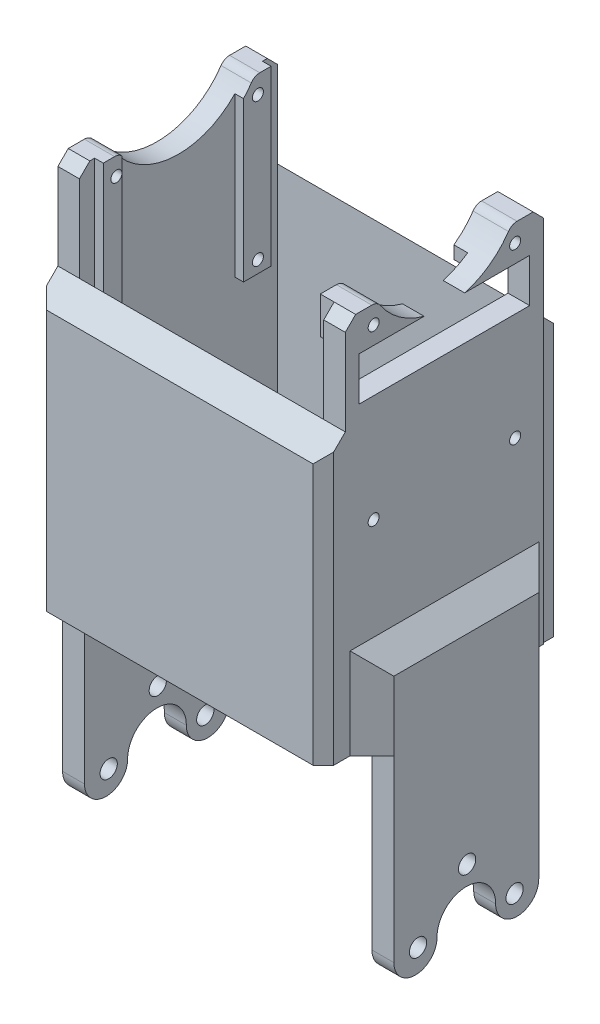
SolidWorks part; units mm, degrees
material "PLA"
ref_plane "Front Plane" through (0, 0, 0) normal (0, 0, 1) x (1, 0, 0)
ref_plane "Top Plane" through (0, 0, 0) normal (0, 1, 0) x (1, 0, 0)
ref_plane "Right Plane" through (0, 0, 0) normal (1, 0, 0) x (0, 0, -1)
sketch "Sketch1" plane through (0, 0, 0) normal (0, 0, 1) x (1, 0, 0)
  line L0 (0, 0) -> (35.4, 0)
  line L1 (35.4, 0) -> (35.4, 51.875)
  line L2 (0, 0) -> (-3.125, 0) construction
  line L3 (35.4, 0) -> (38.525, 0) construction
  line L4 (-3.125, -3.125) -> (38.525, -3.125)
  line L5 (38.525, -3.125) -> (38.525, 51.875)
  line L6 (-3.125, -3.125) -> (-3.125, 51.875)
  line L7 (0, 0) -> (0, 51.875)
  line L8 (0, 51.875) -> (-3.125, 51.875)
  line L9 (35.4, 51.875) -> (38.525, 51.875)
  dimension "D1" = 35.4
  dimension "D2" = 3.125
  dimension "D3" = 3.125
  dimension "D4" = 3.125
  dimension "D5" = 55
  dimension "D6" = 55
extrude "Boss-Extrude1" add sketch "Sketch1" along normal blind 28.72
sketch "Sketch2" plane through (38.525, 0, 0) normal (1, 0, 0) x (0, 0, -1)
  line L0 (-28.72, 46.285) -> (0, 46.285) construction
  line L1 (-28.72, -3.125) -> (-28.72, 51.875) construction
  line L2 (0, -3.125) -> (0, 51.875) construction
  line L3 (-28.72, 51.875) -> (0, 51.875) construction
  line L4 (-14.36, 46.285) -> (-14.36, 57.485) construction
  circle A0 centre (-14.36, 57.485) radius 11.2
  dimension "D1" = 5.59
  dimension "D2" = 11.2
extrude "Cut-Extrude1" cut sketch "Sketch2" against normal through all
fillet "Fillet2" radius 1.5 4 edges at (-1.5625, 51.875, 24.0537) (-1.5625, 51.875, 4.6663) (36.9625, 51.875, 4.6663) (36.9625, 51.875, 24.0537)
sketch "Sketch3" plane through (0, 0, 0) normal (0, 0, -1) x (-1, 0, 0)
  line L1 (-38.325, 37.875) -> (3.125, 37.875)
  line L2 (-38.325, 37.875) -> (-38.325, -3.125)
  line L3 (-38.325, -3.125) -> (3.125, -3.125)
  line L4 (3.125, 37.875) -> (3.125, -3.125)
extrude "Boss-Extrude2" add sketch "Sketch3" along normal blind 3.175
sketch "Sketch4" plane through (0, 0, 28.72) normal (0, 0, 1) x (1, 0, 0)
  line L1 (-3.125, 37.875) -> (38.525, 37.875)
  line L2 (-3.125, 37.875) -> (-3.125, -3.125)
  line L3 (-3.125, -3.125) -> (38.525, -3.125)
  line L4 (38.525, 37.875) -> (38.525, -3.125)
extrude "Boss-Extrude3" add sketch "Sketch4" along normal blind 3.175
chamfer "Chamfer1" distance 3.175 angle 45 2 edges at (17.6, 37.875, -3.175) (17.7, 37.875, 31.895)
chamfer "Chamfer2" distance 1.5 angle 45 4 edges at (-1.5625, 51.875, 0) (36.9625, 51.875, 0) (-1.5625, 51.875, 28.72) (36.9625, 51.875, 28.72)
chamfer "Chamfer3" distance 1.5 angle 45 4 edges at (-3.125, 15.7875, -3.175) (38.325, 15.7875, -3.175) (38.525, 15.7875, 31.895) (-3.125, 15.7875, 31.895)
sketch "Sketch5" plane through (0, 0, 0) normal (1, 0, 0) x (0, 0, -1)
  line L0 (-3.8368, 51.875) -> (-1.5, 51.875) construction
  line L2 (-2.2006, 51.875) -> (-2.2006, 26.7908)
  line L3 (-2.2006, 26.7908) -> (-6.2006, 26.7908)
  line L4 (-6.2006, 49.8127) -> (-6.2006, 26.7908)
  line L6 (-26.5194, 51.875) -> (-26.5194, 26.7908)
  line L7 (-26.5194, 26.7908) -> (-23.7797, 26.7908)
  line L8 (-23.7797, 51.4262) -> (-23.7797, 26.7908)
  line L9 (-27.22, 51.875) -> (-24.8832, 51.875) construction
  line L10 (-3.8368, 51.875) -> (-2.2006, 51.875)
  line L11 (-26.5194, 51.875) -> (-24.8832, 51.875)
  circle A0 centre (-24.61, 49.2608) radius 0.8
  circle A1 centre (-24.61, 28.5608) radius 0.8
  circle A2 centre (-4.11, 28.5608) radius 0.8
  circle A3 centre (-4.11, 49.2608) radius 0.8
  arc A4 (-3.8368, 51.875) -> (-5.0797, 51.2148) centre (-3.8368, 50.375) ccw construction
  arc A5 (-23.6403, 51.2148) -> (-5.0797, 51.2148) centre (-14.36, 57.485) ccw construction
  arc A6 (-23.6403, 51.2148) -> (-24.8832, 51.875) centre (-24.8832, 50.375) ccw construction
  arc A7 (-3.8368, 51.875) -> (-5.0797, 51.2148) centre (-3.8368, 50.375) ccw
  arc A8 (-23.6403, 51.2148) -> (-23.7797, 51.4262) centre (-14.36, 57.485) ccw
  arc A9 (-23.6403, 51.2148) -> (-24.8832, 51.875) centre (-24.8832, 50.375) ccw
  arc A10 (-6.2006, 49.8127) -> (-5.0797, 51.2148) centre (-14.36, 57.485) ccw
  line M8 (-1.5, 51.875) -> (-3.8368, 51.875)
  arc M9 (-3.8368, 51.875) -> (-5.0797, 51.2148) centre (-3.8368, 50.375) ccw
  arc M10 (-5.0797, 51.2148) -> (-23.6403, 51.2148) centre (-14.36, 57.485) cw
  arc M11 (-23.6403, 51.2148) -> (-24.8832, 51.875) centre (-24.8832, 50.375) ccw
  line M12 (-24.8832, 51.875) -> (-27.22, 51.875)
extrude "Boss-Extrude4" add sketch "Sketch5" along normal blind 1.25 contours L4 L3 L2 A3 A2 M10 M8 M9 | L8 L6 L7 A1 A0 M11 M12 region at (0, 39.3275, 25.186) region at (0, 39.1233, 4.1775)
sketch "Sketch6" plane through (0, 0, 0) normal (1, 0, 0) x (0, 0, -1)
  circle A0 centre (-24.61, 49.2608) radius 0.8
  circle A1 centre (-24.61, 28.5608) radius 0.8
  circle A2 centre (-4.11, 28.5608) radius 0.8
  circle A3 centre (-4.11, 49.2608) radius 0.8
extrude "Cut-Extrude2" cut sketch "Sketch6" against normal up to next
sketch "Sketch7" plane through (0, -3.125, 0) normal (0, -1, 0) x (1, 0, 0)
  line L0 (11.7, 22.36) -> (23.7, 22.36) construction
  line L1 (23.7, 22.36) -> (23.7, 6.36) construction
  line L2 (23.7, 6.36) -> (11.7, 6.36) construction
  line L3 (11.7, 6.36) -> (11.7, 22.36) construction
  line L6 (-3.125, 30.395) -> (-3.125, -1.675) construction
  line L7 (-1.625, 31.895) -> (37.025, 31.895) construction
  circle A0 centre (11.7, 22.36) radius 1.35
  circle A1 centre (23.7, 22.36) radius 1.35
  circle A2 centre (23.7, 6.36) radius 1.35
  circle A3 centre (11.7, 6.36) radius 1.35
  dimension "D1" = 2.7
  dimension "D2" = 2.7
  dimension "D3" = 2.7
  dimension "D4" = 2.7
  dimension "D5" = 14.825
  dimension "D6" = 9.535
extrude "Cut-Extrude3" cut sketch "Sketch7" against normal up to next
sketch "Sketch8" plane through (35.4, 0, 0) normal (-1, 0, 0) x (0, 0, 1)
  line L0 (7.86, 48.7133) -> (7.86, 45.9108) construction
  line L1 (1.5, 51.875) -> (5.0709, 51.875)
  line L2 (1.5, 51.875) -> (1.5, 46.5164)
  line L3 (1.5, 46.5164) -> (7.86, 46.5164)
  line L4 (7.86, 48.7133) -> (7.86, 46.5164)
  line L5 (20.86, 45.9108) -> (20.86, 48.7133) construction
  line L6 (20.86, 46.5164) -> (27.22, 46.5164)
  line L7 (20.86, 46.5164) -> (20.86, 48.7133)
  line L8 (23.6491, 51.875) -> (27.22, 51.875)
  line L9 (27.22, 46.5164) -> (27.22, 51.875)
  line L10 (28.72, 0) -> (28.72, 37.875) construction
  line L11 (28.72, 27.0608) -> (0, 27.0608)
  line L12 (28.72, 27.0608) -> (28.72, 22.5608)
  line L13 (28.72, 22.5608) -> (0, 22.5608)
  line L14 (0, 27.0608) -> (0, 22.5608)
  circle A0 centre (24.61, 49.2608) radius 0.8
  circle A1 centre (4.11, 49.2608) radius 0.8
  circle A2 centre (4.11, 24.8108) radius 0.8
  circle A3 centre (24.61, 24.735) radius 0.8758
  arc A4 (5.0077, 51.9796) -> (7.7768, 48.8846) centre (14.36, 57.5608) ccw construction
  arc A5 (5.0709, 51.875) -> (7.7768, 48.8846) centre (14.36, 57.5608) ccw
  arc A6 (20.9432, 48.8846) -> (23.7123, 51.9796) centre (14.36, 57.5608) ccw construction
  arc A7 (20.9432, 48.8846) -> (23.6491, 51.875) centre (14.36, 57.5608) ccw
  spline S0 degree 3 poles (-1990.0282, 140.523) (-63.2874, 38.9164) (7.1505, 51.8916) (8.5344, 45.7425) (-54.2619, 48.1267) (797.0615, -1788.4088) knots -94.086847 -94.086847 -94.086847 -94.086847 0.333333 0.666667 91.791331 91.791331 91.791331 91.791331 weights 1 1 1 1 1 1 only from (7.8374, 48.8108) to (7.86, 48.7133) construction
  spline S1 degree 3 poles (-490.8158, 1985.2839) (-30.2177, -10.261) (5.7924, 51.2853) (9.6673, 46.6143) (-37.1403, 7.4582) (460.9115, -1898.6662) knots -96.396237 -96.396237 -96.396237 -96.396237 0.333333 0.666667 89.616596 89.616596 89.616596 89.616596 weights 1 1 1 1 1 1 only from (7.7768, 48.8846) to (7.8374, 48.8108) construction
  spline S2 degree 3 poles (7.8374, 48.8108) (7.8425, 48.8003) (7.851, 48.7791) (7.8584, 48.746) (7.86, 48.7242) (7.86, 48.7133) knots 0 0 0 0 0.333333 0.666667 1 1 1 1 weights 1 1 1 1 1 1
  spline S3 degree 3 poles (7.7768, 48.8846) (7.785, 48.8784) (7.8005, 48.8647) (7.8213, 48.8396) (7.8325, 48.8208) (7.8374, 48.8108) knots 0 0 0 0 0.333333 0.666667 1 1 1 1 weights 1 1 1 1 1 1
  spline S4 degree 3 poles (356.7329, 2019.8863) (65.3071, 28.7044) (19.6993, 46.3936) (21.999, 51.095) (61.1419, 27.6757) (-1071.4379, -1626.044) knots -39.976297 -39.976297 -39.976297 -39.976297 0.341381 0.67758 38.768425 38.768425 38.768425 38.768425 weights 1 1 1 1 1 1 only from (20.86, 48.7133) to (20.9432, 48.8846) construction
  spline S5 degree 3 poles (20.86, 48.7133) (20.86, 48.7357) (20.8668, 48.7804) (20.896, 48.8401) (20.9264, 48.8718) (20.9432, 48.8846) knots 0 0 0 0 0.341381 0.67758 1 1 1 1 weights 1 1 1 1 1 1
  point P42 (0, 24.8108)
  line M9 (0, 37.875) -> (0, 0)
  line M11 (28.72, 0) -> (28.72, 37.875)
  line M14 (27.22, 51.875) -> (24.8832, 51.875)
  arc M15 (24.8832, 51.875) -> (23.6403, 51.2148) centre (24.8832, 50.375) ccw
  arc M16 (23.6403, 51.2148) -> (5.0797, 51.2148) centre (14.36, 57.485) cw
  arc M17 (5.0797, 51.2148) -> (3.8368, 51.875) centre (3.8368, 50.375) ccw
  line M18 (3.8368, 51.875) -> (1.5, 51.875)
  dimension "D1" = 4.5
extrude "Boss-Extrude5" add sketch "Sketch8" along normal blind 2 contours L6 L9 L7 A0 M14 M15 M16 | L4 L2 L3 A1 M16 M17 M18 | L13 L11 A3 A2 M11 M9 region at (35.4, 49.6068, 22.4374) region at (35.4, 51.7918, 2.6684) region at (35.4, 24.8122, 14.3273)
sketch "Sketch9" plane through (35.4, 0, 0) normal (-1, 0, 0) x (0, 0, 1)
  line L0 (24.61, 50.0607) -> (24.61, 48.4608) construction
  line L1 (4.11, 50.0607) -> (4.11, 48.4608) construction
  line L2 (4.11, 25.6107) -> (4.11, 24.0108) construction
  line L3 (24.61, 25.6107) -> (24.61, 24.0108) construction
  line L4 (26.72, 24.4506) -> (26.72, 51.0993) construction
  line L5 (26.72, 46.6769) -> (2, 46.6769)
  line L6 (26.72, 46.6769) -> (26.72, 40.3691)
  line L7 (26.72, 40.3691) -> (2, 40.3691)
  line L8 (2, 46.6769) -> (2, 40.3691)
  line L9 (2, 51.0993) -> (2, 24.4506) construction
  circle A0 centre (24.61, 24.8107) radius 0.8
  circle A1 centre (4.11, 24.8107) radius 0.8
  circle A2 centre (4.11, 49.2607) radius 0.8
  circle A3 centre (24.61, 49.2607) radius 0.8
extrude "Cut-Extrude4" cut sketch "Sketch9" against normal up to next
sketch "Sketch10" plane through (-3.125, 0, 0) normal (-1, 0, 0) x (0, 0, 1)
  line L0 (3.86, -9.6264) -> (3.86, 3.5377) construction
  line L1 (3.86, -29.0691) -> (3.86, -5.125) construction
  line L2 (24.86, -9.6264) -> (24.86, 3.5377) construction
  line L3 (24.86, -29.0691) -> (24.86, -5.125) construction
  line L4 (30.395, -3.125) -> (-1.675, -3.125) construction
  line L5 (3.86, 6.875) -> (24.86, 6.875)
  line L6 (3.86, 6.875) -> (3.86, -29.0691)
  line L8 (24.86, 6.875) -> (24.86, -29.0691)
  spline S0 degree 3 poles (6.1112, -29.1634) (6.1234, -29.8956) (6.6498, -30.4046) (7.382, -30.3923) knots 0 0 0 0 1 1 1 1 weights 1 0.804738 0.804738 1 construction
  spline S1 degree 3 poles (6.1112, -29.1634) (6.0892, -27.8553) (7.2894, -27.3344) (8.2299, -28.2439) (9.1704, -29.1533) (8.6901, -30.3703) (7.382, -30.3923) knots 0 0 0 0 0.5 0.5 0.5 1 1 1 1 weights 1 0.588456 0.588456 1 0.588456 0.588456 1 construction
  spline S2 degree 3 poles (14.2216, -20.7762) (13.4894, -20.7884) (12.9804, -21.3148) (12.9927, -22.047) knots 0 0 0 0 1 1 1 1 weights 1 0.804738 0.804738 1 construction
  spline S3 degree 3 poles (14.2216, -20.7762) (15.5297, -20.7542) (16.0506, -21.9544) (15.1411, -22.8949) (14.2317, -23.8354) (13.0147, -23.3551) (12.9927, -22.047) knots 0 0 0 0 0.5 0.5 0.5 1 1 1 1 weights 1 0.588456 0.588456 1 0.588456 0.588456 1 construction
  spline S4 degree 3 poles (22.6088, -28.8866) (22.5966, -28.1544) (22.0702, -27.6454) (21.338, -27.6577) knots 0 0 0 0 1 1 1 1 weights 1 0.804738 0.804738 1 construction
  spline S5 degree 3 poles (22.6088, -28.8866) (22.6308, -30.1947) (21.4306, -30.7156) (20.4901, -29.8061) (19.5496, -28.8967) (20.0299, -27.6797) (21.338, -27.6577) knots 0 0 0 0 0.5 0.5 0.5 1 1 1 1 weights 1 0.588456 0.588456 1 0.588456 0.588456 1 construction
  spline S6 degree 3 poles (18.6098, -29.0691) (18.6098, -35.3193) (24.86, -35.3193) (24.86, -29.0691) knots 0 0 0 0 1 1 1 1 weights 1 0.333333 0.333333 1 construction
  spline S7 degree 3 poles (10.1102, -29.0691) (10.0842, -26.5591) (11.8499, -24.775) (14.36, -24.775) (16.8701, -24.775) (18.6358, -26.5591) (18.6098, -29.0691) knots 0 0 0 0 0.5 0.5 0.5 1 1 1 1 weights 1 0.802287 0.802287 1 0.802287 0.802287 1 construction
  spline S8 degree 3 poles (3.86, -29.0691) (3.86, -30.8997) (5.1545, -32.1942) (6.9851, -32.1942) (8.8158, -32.1942) (10.1102, -30.8997) (10.1102, -29.0691) knots 0 0 0 0 0.5 0.5 0.5 1 1 1 1 weights 1 0.804738 0.804738 1 0.804738 0.804738 1 construction
  spline S9 degree 3 poles (6.1112, -29.1634) (6.1234, -29.8956) (6.6498, -30.4046) (7.382, -30.3923) knots 0 0 0 0 1 1 1 1 weights 1 0.804738 0.804738 1
  spline S10 degree 3 poles (6.1112, -29.1634) (6.0892, -27.8553) (7.2894, -27.3344) (8.2299, -28.2439) (9.1704, -29.1533) (8.6901, -30.3703) (7.382, -30.3923) knots 0 0 0 0 0.5 0.5 0.5 1 1 1 1 weights 1 0.588456 0.588456 1 0.588456 0.588456 1
  spline S11 degree 3 poles (14.2216, -20.7762) (13.4894, -20.7884) (12.9804, -21.3148) (12.9927, -22.047) knots 0 0 0 0 1 1 1 1 weights 1 0.804738 0.804738 1
  spline S12 degree 3 poles (14.2216, -20.7762) (15.5297, -20.7542) (16.0506, -21.9544) (15.1411, -22.8949) (14.2317, -23.8354) (13.0147, -23.3551) (12.9927, -22.047) knots 0 0 0 0 0.5 0.5 0.5 1 1 1 1 weights 1 0.588456 0.588456 1 0.588456 0.588456 1
  spline S13 degree 3 poles (22.6088, -28.8866) (22.5966, -28.1544) (22.0702, -27.6454) (21.338, -27.6577) knots 0 0 0 0 1 1 1 1 weights 1 0.804738 0.804738 1
  spline S14 degree 3 poles (22.6088, -28.8866) (22.6308, -30.1947) (21.4306, -30.7156) (20.4901, -29.8061) (19.5496, -28.8967) (20.0299, -27.6797) (21.338, -27.6577) knots 0 0 0 0 0.5 0.5 0.5 1 1 1 1 weights 1 0.588456 0.588456 1 0.588456 0.588456 1
  spline S15 degree 3 poles (18.6098, -29.0691) (18.6098, -35.3193) (24.86, -35.3193) (24.86, -29.0691) knots 0 0 0 0 1 1 1 1 weights 1 0.333333 0.333333 1
  spline S16 degree 3 poles (10.1102, -29.0691) (10.0842, -26.5591) (11.8499, -24.775) (14.36, -24.775) (16.8701, -24.775) (18.6358, -26.5591) (18.6098, -29.0691) knots 0 0 0 0 0.5 0.5 0.5 1 1 1 1 weights 1 0.802287 0.802287 1 0.802287 0.802287 1
  spline S17 degree 3 poles (3.86, -29.0691) (3.86, -30.8997) (5.1545, -32.1942) (6.9851, -32.1942) (8.8158, -32.1942) (10.1102, -30.8997) (10.1102, -29.0691) knots 0 0 0 0 0.5 0.5 0.5 1 1 1 1 weights 1 0.804738 0.804738 1 0.804738 0.804738 1
  dimension "D1" = 10
extrude "Boss-Extrude6" add sketch "Sketch10" along normal blind 3.175
chamfer "Chamfer8" distance 3.175 angle 45 3 edges at (-3.125, 1.875, 3.86) (-3.125, 6.875, 14.36) (-3.125, 1.875, 24.86)
ref_plane "Plane1" through (17.7, 0, 0) normal (1, 0, 0) x (0, 0, -1)
mirror "Mirror2" about plane through (17.7, 0, 0) normal (1, 0, 0) of "Boss-Extrude6"
chamfer "Chamfer9" distance 3.175 angle 45 3 edges at (38.525, 1.875, 24.86) (38.525, 6.875, 14.36) (38.525, 1.875, 3.86)
